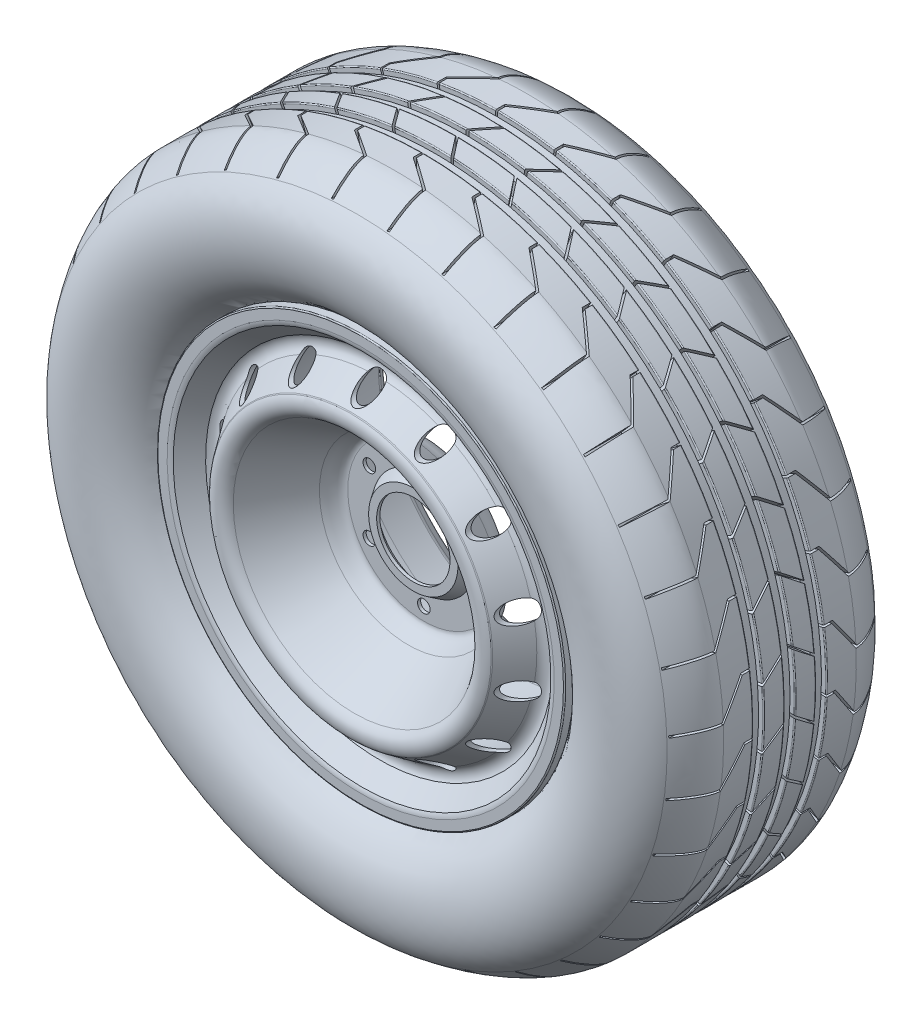
SolidWorks part; units mm, degrees
ref_plane "Front Plane" through (0, 0, 0) normal (0, 0, 1) x (1, 0, 0)
ref_plane "Top Plane" through (0, 0, 0) normal (0, 1, 0) x (1, 0, 0)
ref_plane "Right Plane" through (0, 0, 0) normal (1, 0, 0) x (0, 0, -1)
sketch "Sketch2" plane through (0, 0, 0) normal (1, 0, 0) x (0, 0, -1)
  line L0 (-102.87, 171.5) -> (-102.87, 363.226) construction
  line L1 (-172.4105, 186.5) -> (-187, 186.5)
  line L2 (-188.8982, 188.4974) -> (-188.8982, 190.3713)
  line L3 (-166.106, 313.69) -> (-39.634, 313.69)
  line L4 (-114.6838, 293.9795) -> (-91.0562, 293.9795) construction
  line L5 (-16.8418, 188.4974) -> (-16.8418, 190.3713)
  line L6 (-16.8418, 188.4974) -> (-16.8418, 190.3713)
  line L7 (-33.3295, 186.5) -> (-18.74, 186.5)
  line L8 (0.0002, 0) -> (-150.7743, 0) construction
  line L9 (-163.9409, 313.69) -> (-168.2711, 313.69) construction
  arc A0 (-16.8418, 188.4974) -> (-18.74, 186.5) centre (-18.8418, 188.4974) cw
  arc A1 (-188.8982, 188.4974) -> (-187, 186.5) centre (-186.8982, 188.4974) ccw
  arc A2 (-16.8418, 188.4974) -> (-18.74, 186.5) centre (-18.8418, 188.4974) cw
  spline S0 degree 3 poles (-188.8982, 190.3713) (-187.4149, 194.6515) (-194.521, 198.6578) (-223.7784, 223.3952) (-229.322, 273.7879) (-201.9163, 295.5639) knots 0 0 0 0 0.092594 0.175691 1 1 1 1
  spline S1 degree 3 poles (-201.9163, 295.5639) (-194.6857, 301.6028) (-177.0156, 313.69) (-166.106, 313.69) knots 0 0 0 0 1 1 1 1
  spline S2 degree 3 poles (-102.87, 293.9795) (-122.2086, 293.9795) (-146.8081, 294.4252) (-182.441, 290.3618) (-213.5532, 285.0067) (-215.3462, 259.1729) (-214.3595, 234.0884) (-206.2518, 212.706) (-194.3591, 205.2939) knots 0 0 0 0 0.276163 0.412599 0.589198 0.675863 0.783624 1 1 1 1
  spline S3 degree 3 poles (-194.3591, 205.2939) (-184.6262, 203.6803) (-171.0703, 198.8755) (-172.4105, 186.5) knots 0 0 0 0 1 1 1 1
  spline S4 degree 3 poles (-11.3809, 205.2939) (-21.1138, 203.6803) (-34.6697, 198.8755) (-33.3295, 186.5) knots 0 0 0 0 1 1 1 1
  spline S5 degree 3 poles (-102.87, 293.9795) (-83.5314, 293.9795) (-58.9319, 294.4252) (-23.299, 290.3618) (7.8132, 285.0067) (9.6062, 259.1729) (8.6195, 234.0884) (0.5118, 212.706) (-11.3809, 205.2939) knots 0 0 0 0 0.276163 0.412599 0.589198 0.675863 0.783624 1 1 1 1
  spline S6 degree 3 poles (-3.8237, 295.5639) (-11.0543, 301.6028) (-28.7244, 313.69) (-39.634, 313.69) knots 0 0 0 0 1 1 1 1
  spline S7 degree 3 poles (-16.8418, 190.3713) (-18.3251, 194.6515) (-11.219, 198.6578) (18.0384, 223.3952) (23.582, 273.7879) (-3.8237, 295.5639) knots 0 0 0 0 0.092594 0.175691 1 1 1 1
  point P47 (-102.87, 313.69)
  point P53 (-102.87, 313.69)
  dimension "D1" = 313.69
sketch "Sketch3" plane through (0, 0, 0) normal (1, 0, 0) x (0, 0, -1)
  line L0 (-264.7201, 60) -> (-86.538, 60) construction
  line L1 (0.0002, 0) -> (-150.7743, 0) construction
  line L2 (-268.006, 35) -> (-128.0931, 35) construction
  line L3 (-205.9767, 132.5457) -> (-168.3287, 158.905)
  line L4 (-202.9838, 118.0971) -> (-154.1889, 89.0608)
  line L5 (-138.325, 70.6649) -> (-138.325, 74.3351) construction
  line L6 (-204.5179, 115.519) -> (-153.0125, 84.8698)
  line L7 (-138.325, 72.5) -> (-138.325, 49.129)
  line L8 (-149.8204, 88.8687) -> (-148.4553, 97.5226) construction
  line L9 (-135.325, 72.5) -> (-135.325, 47.5)
  line L10 (-145.325, 41.0069) -> (-135.325, 47.5)
  line L11 (-148.325, 42.6359) -> (-138.325, 49.129)
  line L12 (-148.325, 35) -> (-148.325, 42.6359)
  line L13 (-148.325, 35) -> (-145.325, 35)
  line L14 (-135.325, 69.7933) -> (-135.325, 75.2068) construction
  line L15 (-207.6973, 135.0032) -> (-182.9379, 152.3386)
  line L16 (-207.6973, 135.0032) -> (-208.4087, 134.3022)
  line L17 (-207.6973, 135.0032) -> (-170.0494, 161.3625) construction
  line L18 (-152.5765, 90.65) -> (-151.4186, 97.9901) construction
  line L19 (-102.87, 171.5) -> (-102.87, 0) construction
  line L37 (-18.7062, 174.8816) -> (-18.7062, -14.0227) construction
  line L38 (-19.6768, 162.2421) -> (-50.5335, 160.6051)
  line L39 (-8.6133, 169.732) -> (-16.5029, 163.5956)
  line L40 (-3.2572, 181.7244) -> (-6.3673, 172.9513)
  line L41 (-2.4789, 190.0232) -> (-2.4789, 185.1993)
  line L50 (-145.325, 35) -> (-145.325, 41.0069)
  line L62 (-50.5335, 160.6051) -> (-168.3287, 158.905)
  line L63 (-15.8487, 193.5755) -> (-8.0026, 193.5755)
  line L64 (-16.5655, 188.0964) -> (-16.5655, 192.8587)
  line L65 (-21.0323, 177.6907) -> (-17.0667, 186.277)
  line L66 (-29.906, 169.8214) -> (-23.0413, 175.1606)
  line L67 (-60.5422, 168.7285) -> (-33.1346, 168.7285)
  line L68 (-197.2477, 180.0601) -> (-180.6139, 165.7725)
  line L69 (-198.5359, 193.3989) -> (-198.5359, 184.567)
  line L70 (-189.9573, 194.491) -> (-197.4438, 194.491)
  line L71 (-188.9775, 188.7534) -> (-188.9775, 193.5112)
  line L72 (-180.6139, 175.9717) -> (-187.2992, 184.567)
  line L73 (-177.2296, 173.7879) -> (-180.6139, 175.9717)
  line L74 (-60.5422, 168.7285) -> (-164.6364, 169.6441)
  line L75 (-138.325, 72.5) -> (-138.325, 49.129) construction
  arc A0 (-205.9767, 132.5457) -> (-202.9838, 118.0971) centre (-197.87, 126.6906) ccw
  arc A1 (-180.6139, 165.7725) -> (-182.9379, 152.3386) centre (-188.4928, 160.2175) cw
  arc A2 (-208.4087, 134.3022) -> (-204.5179, 115.519) centre (-197.87, 126.6906) ccw
  arc A4 (-205.9767, 132.5457) -> (-202.9838, 118.0971) centre (-197.87, 126.6906) ccw construction
  arc A5 (-154.1889, 89.0608) -> (-152.5765, 90.65) centre (-146.8356, 83.2127) cw construction
  arc A19 (-198.5359, 193.3989) -> (-197.4438, 194.491) centre (-197.3457, 193.3009) cw
  arc A20 (-188.9775, 193.5112) -> (-189.9573, 194.491) centre (-190.0696, 193.3989) ccw
  arc A21 (-15.8487, 193.5755) -> (-16.5655, 192.8587) centre (-15.8203, 192.8303) ccw
  arc A22 (-2.4789, 190.0232) -> (-8.0026, 193.5755) centre (-5.2407, 191.7993) ccw
  arc A23 (-29.906, 169.8214) -> (-33.1346, 168.7285) centre (-32.7758, 172.9841) cw
  arc A24 (-19.6768, 162.2421) -> (-16.5029, 163.5956) centre (-20.3064, 168.1163) ccw
  arc A31 (-198.5359, 184.567) -> (-197.2477, 180.0601) centre (-188.1081, 185.11) ccw
  arc A32 (-188.9775, 188.7534) -> (-187.2992, 184.567) centre (-182.2724, 189.0119) ccw
  arc A33 (-164.6364, 169.6441) -> (-177.2296, 173.7879) centre (-165.4833, 188.2776) cw
  arc A34 (-23.0413, 175.1606) -> (-21.0323, 177.6907) centre (-28.4573, 181.5237) ccw
  arc A35 (-16.5655, 188.0964) -> (-17.0667, 186.277) centre (-19.6313, 187.9621) cw
  arc A36 (-6.3673, 172.9513) -> (-8.6133, 169.732) centre (-12.4381, 174.7936) cw
  arc A37 (-2.4789, 185.1993) -> (-3.2572, 181.7244) centre (-8.967, 184.8279) cw
  arc A38 (-153.0125, 84.8698) -> (-149.8204, 88.8687) centre (-146.8356, 83.2127) cw construction
  spline S1 degree 3 poles (-153.0125, 84.8698) (-151.0641, 83.7104) (-144.2655, 80.5424) (-138.325, 76.2907) (-138.325, 72.5) knots 0 0 0 0 0.479313 1 1 1 1
  spline S2 degree 3 poles (-154.1889, 89.0608) (-147.1802, 84.8902) (-141.0576, 83.9707) (-135.325, 76.3082) (-135.325, 72.5) knots 0 0 0 0 0.640505 1 1 1 1
  dimension "D1" = 60
  dimension "D3" = 10
  dimension "D4" = 42.455
  dimension "D10" = 3
  dimension "D2" = 35
  dimension "D6" = 25
  dimension "D7" = 10
  dimension "D8" = 95
  dimension "D5" = 3
  dimension "D9" = 3
revolve "Revolve2" add sketch "Sketch3" angle 360 about L8
sketch "Sketch6" plane through (0, 0, 0) normal (1, 0, 0) x (0, 0, -1)
  line L0 (-102.87, 171.5) -> (-102.87, -118.6175) construction
ref_plane "Plane1" through (0, 0, 258.5359) normal (0, 0, 1) x (1, 0, 0)
sketch "Sketch4" plane through (0, 0, 258.5359) normal (0, 0, 1) x (1, 0, 0)
  circle A0 centre (0, 147) radius 10
  circle A1 centre (63.7809, 132.4424) radius 10
  circle A2 centre (114.9292, 91.653) radius 10
  circle A3 centre (143.3144, 32.7106) radius 10
  circle A4 centre (143.3144, -32.7106) radius 10
  circle A5 centre (114.9292, -91.653) radius 10
  circle A6 centre (63.7809, -132.4424) radius 10
  circle A7 centre (0, -147) radius 10
  circle A8 centre (-63.7809, -132.4424) radius 10
  circle A9 centre (-114.9292, -91.653) radius 10
  circle A10 centre (-143.3144, -32.7106) radius 10
  circle A11 centre (-143.3144, 32.7106) radius 10
  circle A12 centre (-114.9292, 91.653) radius 10
  circle A13 centre (-63.7809, 132.4424) radius 10
  point P31 (0, 0)
  dimension "D1" = 20
  dimension "D2" = 147
  dimension "D3" = 14
extrude "Cut-Extrude1" cut sketch "Sketch4" against normal blind 280
sketch "Sketch5" plane through (0, 0, 138.325) normal (0, 0, 1) x (1, 0, 0)
  circle A0 centre (0, 60) radius 6
  circle A1 centre (51.9615, 30) radius 6
  circle A2 centre (51.9615, -30) radius 6
  circle A3 centre (0, -60) radius 6
  circle A4 centre (-51.9615, -30) radius 6
  circle A5 centre (-51.9615, 30) radius 6
  point P13 (0, 0)
  point P14 (0, 0)
  point P15 (0, 0)
  dimension "D1" = 12
  dimension "D2" = 60
  dimension "D3" = 6
extrude "Cut-Extrude2" cut sketch "Sketch5" against normal through all
revolve "Revolve3" add sketch "Sketch2" angle 360 about L8 region at (0, 189.1767, 179.7052)
sketch "Sketch8" plane through (0, 0, 0) normal (1, 0, 0) x (0, 0, -1)
  line L0 (-102.87, 313.69) -> (-102.87, 255.2302) construction
  line L1 (-39.634, 313.69) -> (-166.106, 313.69) construction
  line L2 (-137.87, 308.69) -> (-127.87, 308.69)
  line L3 (-107.87, 313.69) -> (-97.87, 313.69)
  line L4 (-107.87, 313.69) -> (-107.87, 308.69)
  line L5 (-107.87, 308.69) -> (-97.87, 308.69)
  line L6 (-97.87, 313.69) -> (-97.87, 308.69)
  line L7 (-137.87, 313.69) -> (-127.87, 313.69)
  line L8 (-137.87, 313.69) -> (-137.87, 308.69)
  line L9 (-127.87, 313.69) -> (-127.87, 308.69)
  line L10 (-77.87, 308.69) -> (-67.87, 308.69)
  line L11 (-77.87, 313.69) -> (-67.87, 313.69)
  line L12 (-77.87, 313.69) -> (-77.87, 308.69)
  line L13 (-67.87, 313.69) -> (-67.87, 308.69)
  dimension "D1" = 10
  dimension "D2" = 5
  dimension "D3" = 2
  dimension "D4" = 2
revolve "Cut-Revolve1" cut sketch "Sketch8" angle 360 about axis through (0, 0, 168.3287) along (0, 0, 1)
ref_plane "Plane3" through (0, 320, 0) normal (0, 1, 0) x (1, 0, 0)
fillet "Fillet1" radius 1 6 edges at (0, 313.69, 137.87) (0, 313.69, 127.87) (0, 313.69, 107.87) (0, 313.69, 97.87) (0, 313.69, 77.87) (0, 313.69, 67.87)
sketch "Sketch9" plane through (0, 320, 0) normal (0, 1, 0) x (1, 0, 0)
  line L0 (0, -220.6296) -> (0, 14.8896) construction
  line L1 (-253.3411, -220.6296) -> (253.3411, -220.6296) construction
  line L2 (253.3411, 14.8896) -> (-253.3411, 14.8896) construction
  line L3 (0, -137.87) -> (0, -145.4463)
  line L4 (313.69, -137.87) -> (-313.69, -137.87) construction
  line L5 (0, -145.4463) -> (29.5915, -166.106)
  line L6 (313.69, -166.106) -> (-313.69, -166.106) construction
  line L7 (29.5915, -166.106) -> (29.5915, -220.6296)
  line L8 (-2, -137.87) -> (-2, -146.4892)
  line L9 (-2, -146.4892) -> (27.5915, -167.1489)
  line L10 (27.5915, -167.1489) -> (27.5915, -220.6296)
  line L11 (27.5915, -220.6296) -> (29.5915, -220.6296)
  line L12 (-2, -137.87) -> (0, -137.87)
  line L13 (-308.69, -102.87) -> (308.69, -102.87) construction
  line L14 (-308.69, -97.87) -> (-308.69, -107.87) construction
  line L15 (308.69, -107.87) -> (308.69, -97.87) construction
  line L16 (-2, -67.87) -> (0, -67.87)
  line L17 (27.5915, 14.8896) -> (29.5915, 14.8896)
  line L18 (27.5915, -38.5911) -> (27.5915, 14.8896)
  line L19 (-2, -59.2508) -> (27.5915, -38.5911)
  line L20 (-2, -67.87) -> (-2, -59.2508)
  line L21 (29.5915, -39.634) -> (29.5915, 14.8896)
  line L22 (0, -60.2937) -> (29.5915, -39.634)
  line L23 (0, -67.87) -> (0, -60.2937)
  line L24 (0, -50.5335) -> (0, -168.3287) construction
  line L25 (0, -107.87) -> (15.389, -127.87)
  line L26 (312.69, -107.87) -> (-312.69, -107.87) construction
  line L27 (-308.69, -127.87) -> (308.69, -127.87) construction
  line L28 (2.5235, -107.87) -> (17.9125, -127.87)
  line L29 (0, -107.87) -> (2.5235, -107.87)
  line L30 (15.389, -127.87) -> (17.9125, -127.87)
  line L31 (1.5851, -106.6504) -> (16.974, -126.6504) construction
  line L32 (15.389, -77.87) -> (17.9125, -77.87)
  line L33 (0, -97.87) -> (2.5235, -97.87)
  line L34 (2.5235, -97.87) -> (17.9125, -77.87)
  line L35 (0, -97.87) -> (15.389, -77.87)
  dimension "D1" = 2
  dimension "D2" = 2
extrude "Cut-Extrude3" cut sketch "Sketch9" against normal blind 25
pattern_circular "CirPattern1" count 35 over 360 about axis through (0, 0, 168.3287) along (0, 0, 1) of "Cut-Extrude3"
